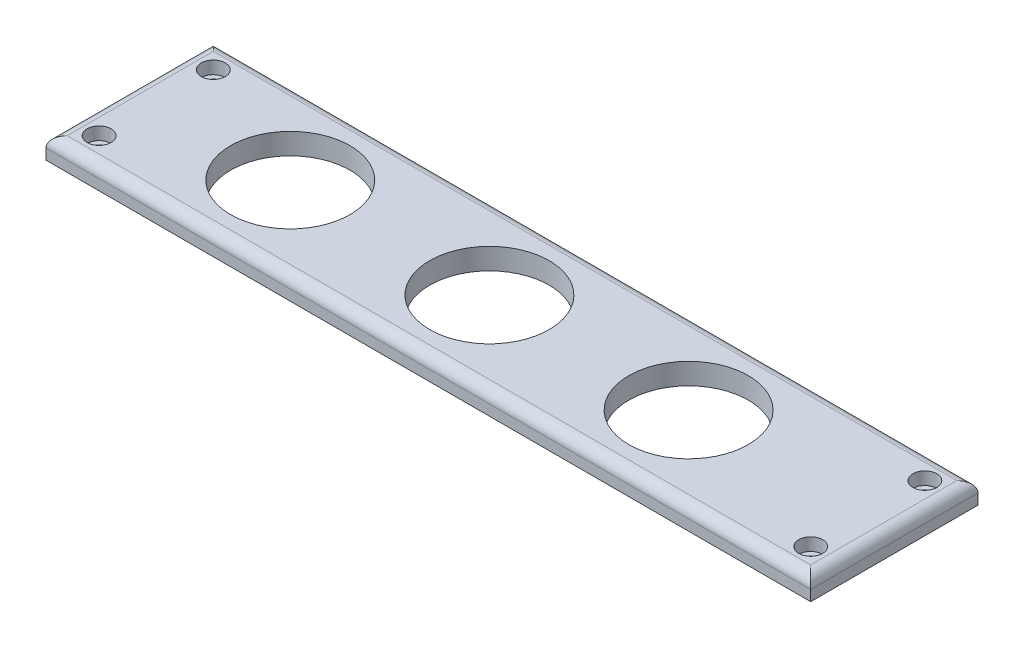
SolidWorks part; units mm, degrees
ref_plane "Front Plane" through (0, 0, 0) normal (0, 0, 1) x (1, 0, 0)
ref_plane "Top Plane" through (0, 0, 0) normal (0, 1, 0) x (1, 0, 0)
ref_plane "Right Plane" through (0, 0, 0) normal (1, 0, 0) x (0, 0, -1)
other "Configuration Table"
sketch "Эскиз1" plane through (0, 0, 0) normal (0, 1, 0) x (1, 0, 0)
  line L1 (0, 0) -> (288, 0)
  line L2 (0, 0) -> (0, 63)
  line L3 (0, 63) -> (288, 63)
  line L4 (288, 0) -> (288, 63)
extrude "Бобышка-Вытянуть1" add sketch "Эскиз1" along normal blind 8 contours L2 L1 L4 L3
sketch "Эскиз2" plane through (0, 8, 0) normal (0, 1, 0) x (1, 0, 0)
  line L3 (0, 0) -> (38, 0) construction
  line L4 (0, 0) -> (288, 0) construction
  line L5 (38, 0) -> (38, 63) construction
  line L6 (0, 63) -> (288, 63) construction
  line L7 (38, 0) -> (60.5, 0) construction
  line L8 (60.5, 0) -> (60.5, 63) construction
  line L9 (83, 63) -> (83, 0) construction
  line L10 (288, 0) -> (233, 0)
  line L11 (233, 0) -> (233, 63) construction
  line L12 (60.5, 31.5) -> (210.5, 31.5) construction
  circle A0 centre (60.5, 31.5) radius 22.5
  circle A1 centre (210.5, 31.5) radius 22.5
  circle A2 centre (135.5, 31.5) radius 22.5
extrude "Вырез-Вытянуть1" cut sketch "Эскиз2" against normal blind 8 contours A0
extrude "Вырез-Вытянуть2" cut sketch "Эскиз2<3>" against normal blind 8 contours A2
sketch "Эскиз2<3>" plane through (0, 8, 0) normal (0, 1, 0) x (1, 0, 0) same geometry as "Эскиз2"
extrude "Вырез-Вытянуть3" cut sketch "Эскиз2<4>" against normal blind 8 contours A1
sketch "Эскиз2<4>" plane through (0, 8, 0) normal (0, 1, 0) x (1, 0, 0) same geometry as "Эскиз2"
fillet "Скругление4" radius 4 4 edges at (144, 8, -63) (0, 8, -31.5) (144, 8, 0) (288, 8, -31.5) type face fillet first side face at (210.5, 8, -9) second side face at (144, 4, -63) second side face at (288, 4, -31.5) second side face at (0, 4, -31.5) second side face at (144, 4, 0)
sketch "Эскиз3" plane through (0, 8, 0) normal (0, 1, 0) x (1, 0, 0)
  line L0 (4, 59) -> (10, 53) construction
  line L1 (4, 4) -> (10, 10) construction
  line L2 (4, 4) -> (284, 4) construction
  line L3 (284, 4) -> (278, 10) construction
  line L4 (284, 59) -> (278, 53) construction
  circle A0 centre (10, 53) radius 4.5
  circle A1 centre (10, 53) radius 2.5
  circle A2 centre (10, 10) radius 4.5
  circle A3 centre (10, 10) radius 2.5
  circle A4 centre (278, 10) radius 4.5
  circle A5 centre (278, 10) radius 2.5
  circle A6 centre (278, 53) radius 4.5
  circle A7 centre (278, 53) radius 2.5
  point P3 (278.305, 10)
  point P21 (284, 59)
extrude "Вырез-Вытянуть4" cut sketch "Эскиз3" against normal through all contours A3 | A1
extrude "Вырез-Вытянуть5" cut sketch "Эскиз3<3>" against normal blind 4.8 contours A2 | A0 | A4 | A6
sketch "Эскиз3<3>" plane through (0, 8, 0) normal (0, 1, 0) x (1, 0, 0) same geometry as "Эскиз3"
extrude "Вырез-Вытянуть6" cut sketch "Эскиз3<4>" against normal through all contours A7 | A5
sketch "Эскиз3<4>" plane through (0, 8, 0) normal (0, 1, 0) x (1, 0, 0) same geometry as "Эскиз3"
